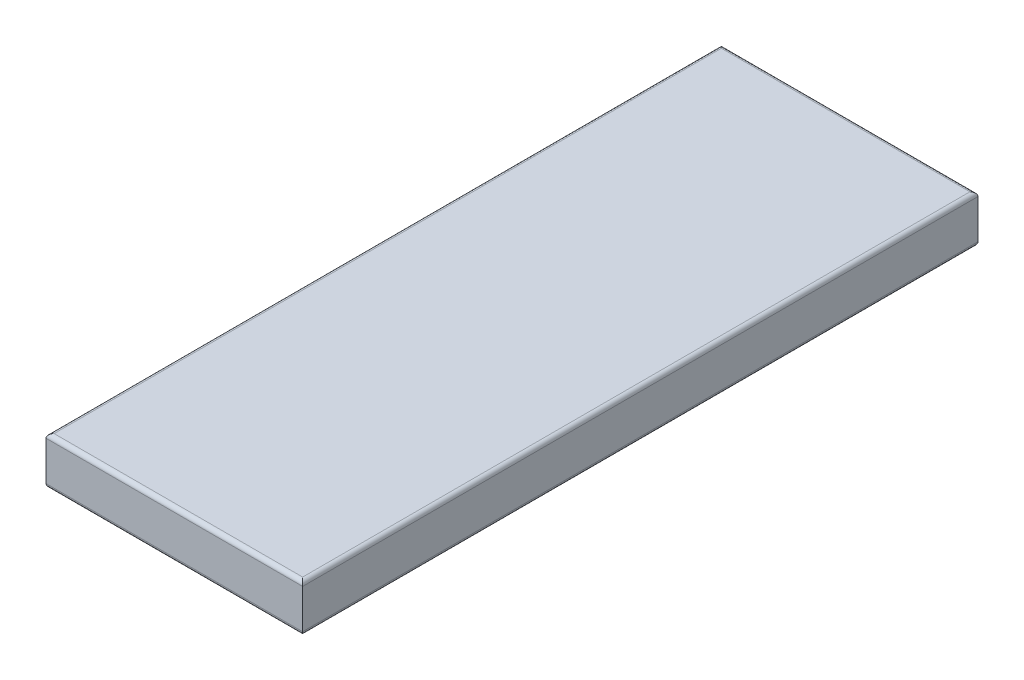
SolidWorks part; units mm, degrees
material "Никель"
ref_plane "Спереди" through (0, 0, 0) normal (0, 0, 1) x (1, 0, 0)
ref_plane "Сверху" through (0, 0, 0) normal (0, 1, 0) x (1, 0, 0)
ref_plane "Справа" through (0, 0, 0) normal (1, 0, 0) x (0, 0, -1)
sketch "Эскиз1" plane through (0, 0, 0) normal (0, 0, 1) x (1, 0, 0)
  line L1 (-9.5, 1.75) -> (9.5, 1.75)
  line L2 (-9.5, 1.75) -> (-9.5, -1.75)
  line L3 (-9.5, -1.75) -> (9.5, -1.75)
  line L4 (9.5, 1.75) -> (9.5, -1.75)
  line L5 (0, -1.75) -> (0, 1.75) construction
  line L6 (-9.5, 0) -> (9.5, 0) construction
  point P0 (0, 0)
  dimension "D1" = 3.5
  dimension "D2" = 19
extrude "Бобышка-Вытянуть1" add sketch "Эскиз1" along normal blind 50
fillet "Скругление1" radius 0.3 8 edges at (-9.5, -1.75, 25) (0, -1.75, 50) (9.5, -1.75, 25) (0, -1.75, 0) (9.5, 1.75, 25) (0, 1.75, 50) (-9.5, 1.75, 25) (0, 1.75, 0)
